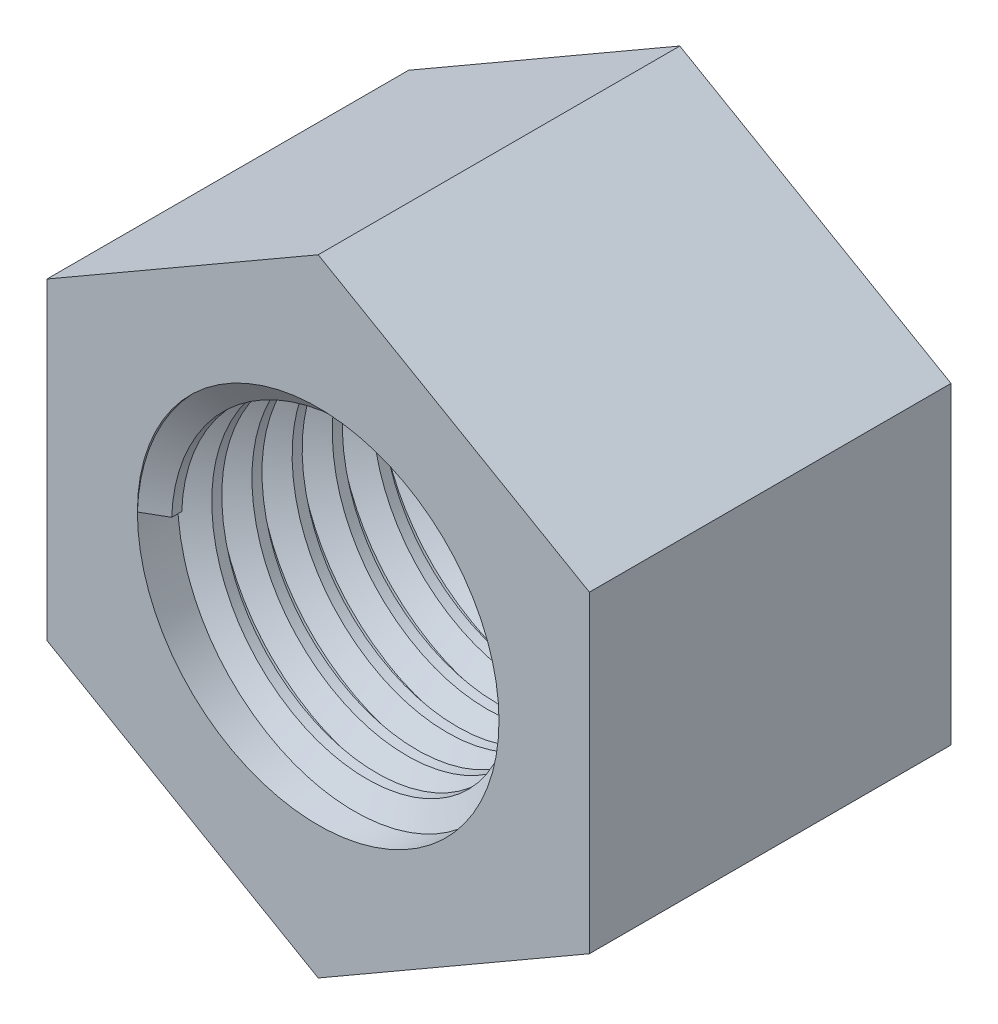
SolidWorks part; units mm, degrees
ref_plane "Front Plane" through (0, 0, 0) normal (0, 0, 1) x (1, 0, 0)
ref_plane "Top Plane" through (0, 0, 0) normal (0, 1, 0) x (1, 0, 0)
ref_plane "Right Plane" through (0, 0, 0) normal (1, 0, 0) x (0, 0, -1)
sketch "Sketch1" plane through (0, 0, 0) normal (0, 0, 1) x (1, 0, 0)
  line L0 (-19.507, 0) -> (19.507, 0) construction
  line L1 (0, -20.2151) -> (0, 20.2151) construction
  line L3 (0, 8.2489) -> (-7.1438, 4.1244)
  line L4 (-7.1438, 4.1244) -> (-7.1437, -4.1244)
  line L5 (-7.1437, -4.1244) -> (0, -8.2489)
  line L6 (0, -8.2489) -> (7.1438, -4.1244)
  line L7 (7.1438, -4.1244) -> (7.1437, 4.1244)
  line L8 (7.1437, 4.1244) -> (0, 8.2489)
  circle A0 centre (0, 0) radius 7.1438 construction
  circle A1 centre (0, 0) radius 4.7625
  point P4 (0, 0)
  point P8 (0, 0)
  dimension "D2" = 9.525
  dimension "D1" = 14.2875
extrude "Boss-Extrude1" add sketch "Sketch1" along normal mid plane 9.525
thread "Thread1" pitch 1.0583 method extrude profile "Thread Profile2" start angle 0, offset 0, length 9.525, pitch 1.0583, diameter 9.525
ref_plane "Plane2" through (-4.7625, 0, 4.7625) normal (0, -1, 0) x (-1, 0, 0)
sketch "Thread Profile2" plane through (-4.7625, 0, 4.7625) normal (0, -1, 0) x (-1, 0, 0)
  line L0 (0, 0) -> (0, 1.0583) construction
  line L11 (0, 0) -> (0, 0.926)
  line L12 (0, 0.926) -> (-0.5728, 0.5953)
  line L13 (-0.5728, 0.5953) -> (-0.5728, 0.3307)
  line L15 (-0.5728, 0.3307) -> (0, 0)
  line L17 (-0.5728, 0.463) -> (0, 0.463) construction
  point P2 (0, 0)
  dimension "Pitch" = 1.0583
  dimension "Profile_Angle" = 60
  dimension "Profile_Land" = 0.2646
  dimension "Profile_Height" = 0.5728
